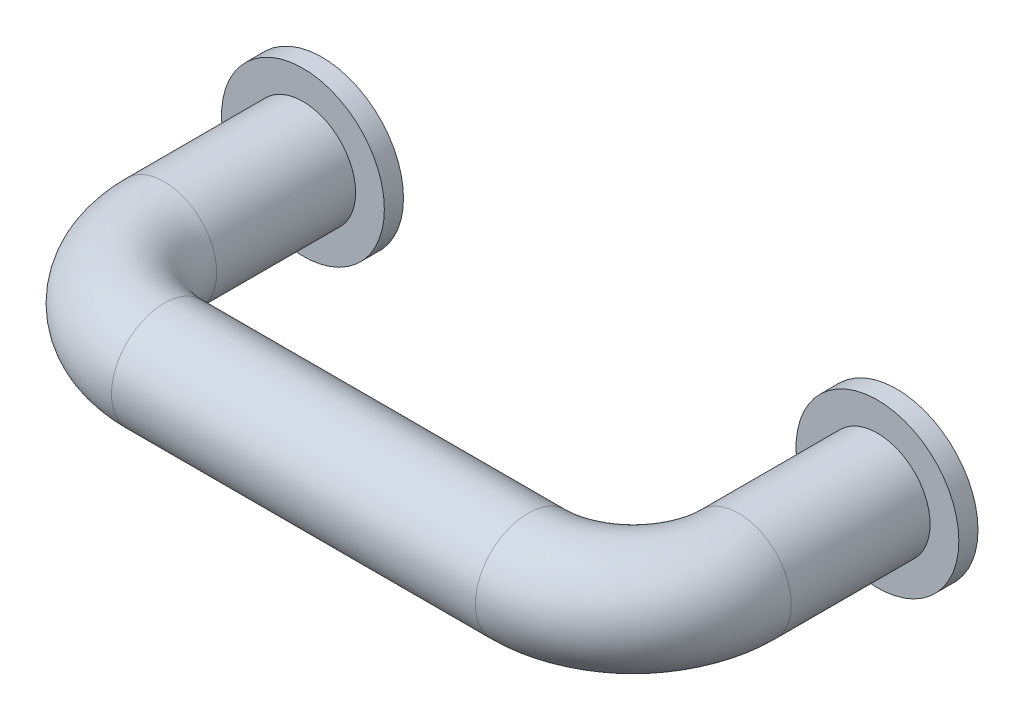
SolidWorks part; units mm, degrees
material "AISI 316 Annealed Stainless Steel Bar (SS)"
ref_plane "Front Plane" through (0, 0, 0) normal (0, 0, 1) x (1, 0, 0)
ref_plane "Top Plane" through (0, 0, 0) normal (0, 1, 0) x (1, 0, 0)
ref_plane "Right Plane" through (0, 0, 0) normal (1, 0, 0) x (0, 0, -1)
sketch3d "Pipe path 1"
  line L0 (-60, 0, 0) -> (-60, 0, 33)
  line L1 (-38, 0, 55) -> (38, 0, 55)
  line L2 (60, 0, 33) -> (60, 0, 0)
  arc A0 (-60, 0, 33) -> (-38, 0, 55) centre (-38, 0, 33) ccw
  arc A1 (38, 0, 55) -> (60, 0, 33) centre (38, 0, 33) ccw
  point P6 (-60, 0, 55)
  point P7 (-38, 22, 33)
  point P10 (60, 0, 55)
  point P11 (38, 22, 33)
  dimension "D1" = 22
  dimension "D2" = 22
sweep "Pipe 1" add path "Pipe path 1" circular profile diameter 22 parameters "D3"=22
sketch "Extrude sketch 1" plane through (0, 0, 0) normal (0, 0, 1) x (1, 0, 0)
  circle A0 centre (-60, 0) radius 17
  dimension "D1" = 34
extrude "Extrude 1" add sketch "Extrude sketch 1" along normal blind 4 separate body
sketch "Extrude sketch 2" plane through (0, 0, 0) normal (0, 0, 1) x (1, 0, 0)
  circle A0 centre (60, 0) radius 17
  dimension "D1" = 34
extrude "Extrude 2" add sketch "Extrude sketch 2" along normal blind 4 separate body
combine bodies "Combine (weld / assembly of features)" operation type add bodies to combine 102 103 101
